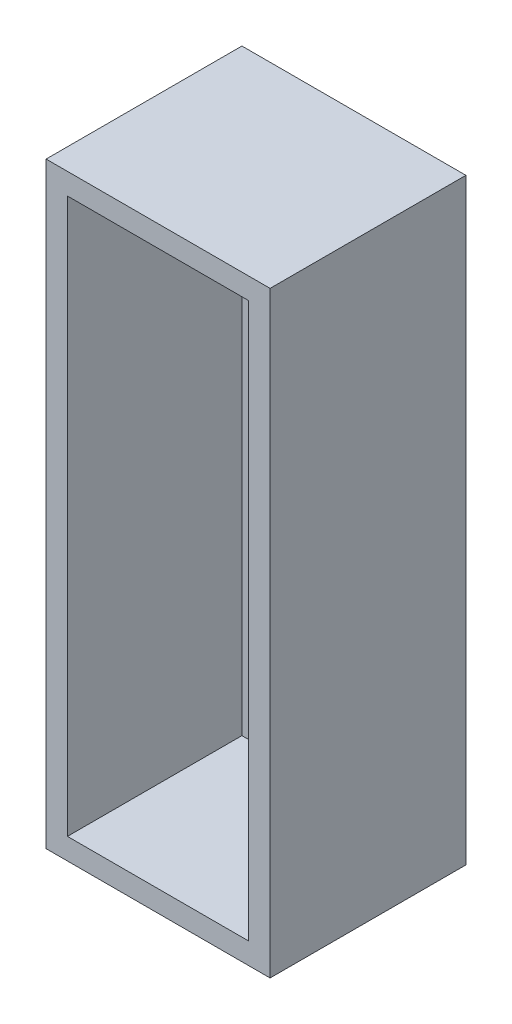
SolidWorks part; units mm, degrees
ref_plane "Front Plane" through (0, 0, 0) normal (0, 0, 1) x (1, 0, 0)
ref_plane "Top Plane" through (0, 0, 0) normal (0, 1, 0) x (1, 0, 0)
ref_plane "Right Plane" through (0, 0, 0) normal (1, 0, 0) x (0, 0, -1)
sketch "Sketch1" plane through (0, 0, 0) normal (0, 0, 1) x (1, 0, 0)
  line L1 (0, 0) -> (107.95, 0)
  line L2 (0, 0) -> (0, 330.2)
  line L3 (0, 330.2) -> (107.95, 330.2)
  line L4 (107.95, 0) -> (107.95, 330.2)
  line L5 (-12.7, -12.7) -> (120.65, -12.7)
  line L6 (-12.7, -12.7) -> (-12.7, 342.9)
  line L7 (-12.7, 342.9) -> (120.65, 342.9)
  line L8 (120.65, -12.7) -> (120.65, 342.9)
  dimension "D1" = 330.2
  dimension "D2" = 107.95
  dimension "D3" = 355.6
  dimension "D4" = 12.7
  dimension "D5" = 12.7
  dimension "D6" = 12.7
extrude "Boss-Extrude1" add sketch "Sketch1" along normal blind 12.7 contours L1 L4 L3 L2 | L5 L8 L7 L6 L4 L1 L2 L3 region at (53.975, 165.1, 0) region at (-8.9022, 165.1, 0)
extrude "Boss-Extrude2" add sketch "Sketch1<3>" along normal blind 116.586
sketch "Sketch1<3>" plane through (0, 0, 0) normal (0, 0, 1) x (1, 0, 0) same geometry as "Sketch1"
